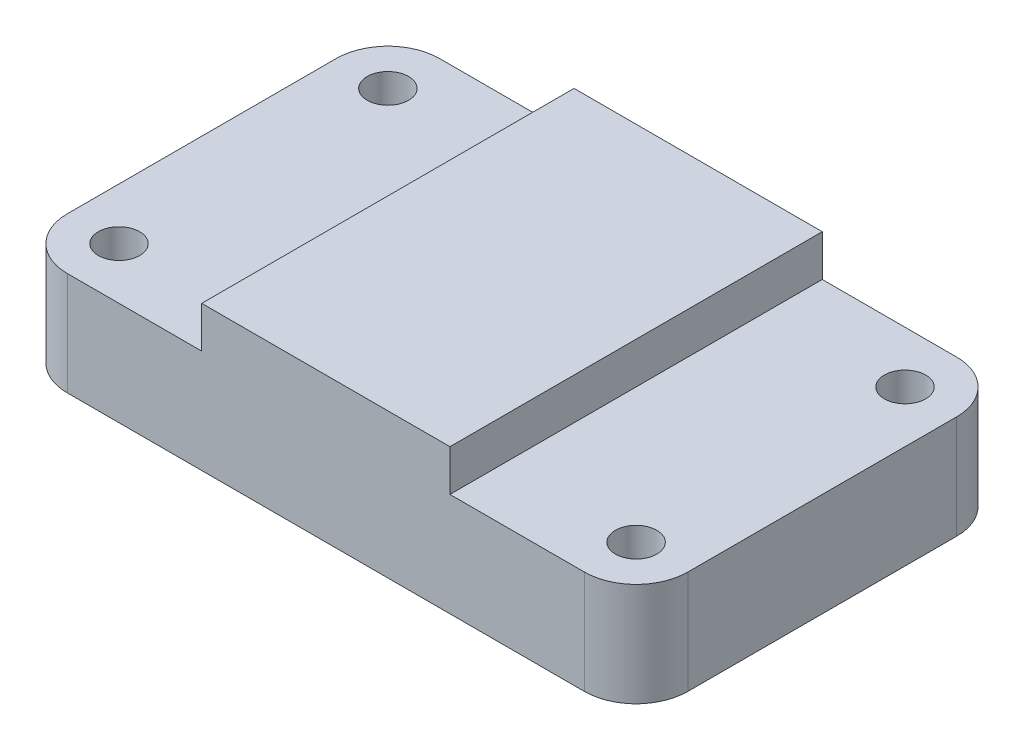
SolidWorks part; units mm, degrees
ref_plane "Front" through (0, 0, 0) normal (0, 0, 1) x (1, 0, 0)
ref_plane "Top" through (0, 0, 0) normal (0, 1, 0) x (1, 0, 0)
ref_plane "Right" through (0, 0, 0) normal (1, 0, 0) x (0, 0, -1)
sketch "Esquisse1" plane through (0, 0, 0) normal (0, 1, 0) x (1, 0, 0)
  line L0 (-60, 90) -> (-60, -90)
  line L1 (125, -90) -> (-125, -90)
  line L2 (150, -65) -> (150, 65)
  line L3 (125, 90) -> (-125, 90)
  line L4 (-150, -65) -> (-150, 65)
  line L5 (150, -90) -> (-150, 90) construction
  line L6 (150, 90) -> (-150, -90) construction
  line L7 (0, -90) -> (0, 90) construction
  line L8 (60, 90) -> (60, -90)
  arc A0 (-125, -90) -> (-150, -65) centre (-125, -65) cw
  arc A1 (125, -90) -> (150, -65) centre (125, -65) ccw
  arc A2 (150, 65) -> (125, 90) centre (125, 65) ccw
  arc A3 (-125, 90) -> (-150, 65) centre (-125, 65) ccw
  circle A4 centre (-125, 65) radius 10
  circle A5 centre (125, 65) radius 10
  circle A6 centre (125, -65) radius 10
  circle A7 centre (-125, -65) radius 10
  point P0 (0, 0)
  point P27 (0, 0)
  dimension "D3" = 25
  dimension "D4" = 20
  dimension "D1" = 180
  dimension "D2" = 300
  dimension "D5" = 60
extrude "Boss.-Extru.1" add sketch "Esquisse1" along normal blind 50 contours L3 A3 L4 A0 L1 L0 A7 A4 | L2 A2 L3 L8 L1 A1 A6 A5 region at (-103.4879, 0, 0) region at (103.4879, 0, 0)
extrude "Boss.-Extru.2" add sketch "Esquisse1<3>" along normal blind 70 contours L8 L3 L0 L1 region at (0, 0, 0)
sketch "Esquisse1<3>" plane through (0, 0, 0) normal (0, 1, 0) x (1, 0, 0) same geometry as "Esquisse1"
ref_plane "Plan1" through (-150, 0, -65) normal (0, 0, -1) x (-1, 0, 0)
